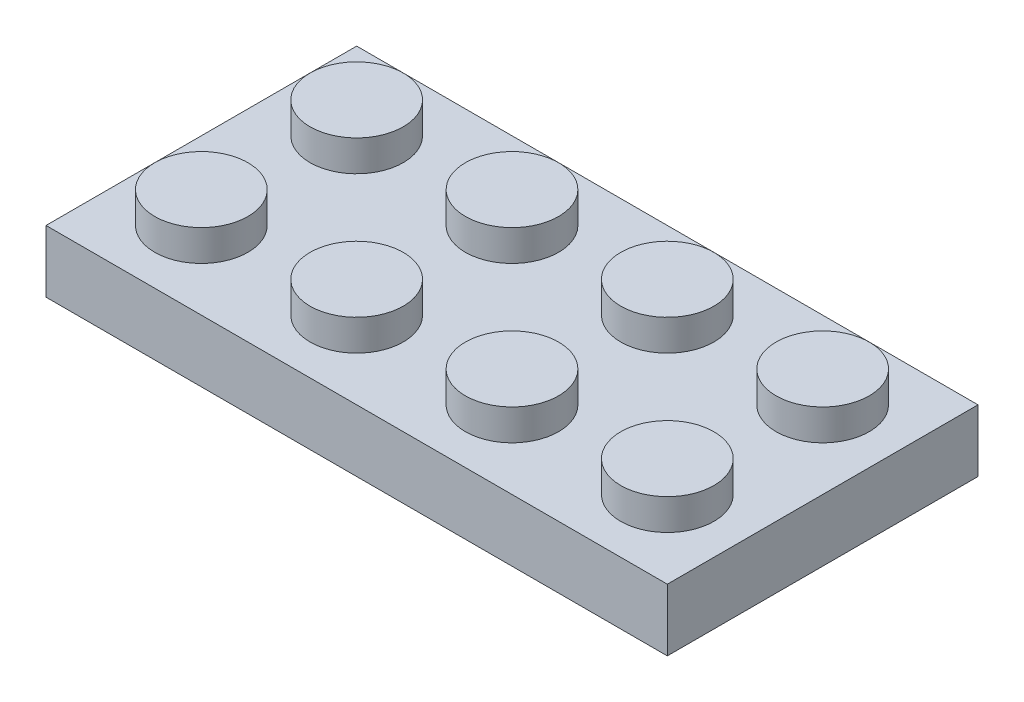
SolidWorks part; units mm, degrees
ref_plane "Front Plane" through (0, 0, 0) normal (0, 0, 1) x (1, 0, 0)
ref_plane "Top Plane" through (0, 0, 0) normal (0, 1, 0) x (1, 0, 0)
ref_plane "Right Plane" through (0, 0, 0) normal (1, 0, 0) x (0, 0, -1)
sketch "Sketch1" plane through (0, 0, 0) normal (0, 1, 0) x (1, 0, 0)
  line L1 (-10, -5) -> (10, -5)
  line L2 (-10, -5) -> (-10, 5)
  line L3 (-10, 5) -> (10, 5)
  line L4 (10, -5) -> (10, 5)
  line L5 (-10, -5) -> (10, 5) construction
  line L6 (-10, 5) -> (10, -5) construction
  line L7 (-9, -4) -> (9, -4)
  line L8 (-9, -4) -> (-9, 4)
  line L9 (-9, 4) -> (9, 4)
  line L10 (9, -4) -> (9, 4)
  line L11 (-9, -4) -> (9, 4) construction
  line L12 (-9, 4) -> (9, -4) construction
  circle A0 centre (-2.5, 2.5) radius 1.5
  circle A1 centre (-7.5, 2.5) radius 1.5
  circle A2 centre (2.5, 2.5) radius 1.5
  circle A3 centre (7.5, 2.5) radius 1.5
  circle A4 centre (-2.5, -2.5) radius 1.5
  circle A5 centre (2.5, -2.5) radius 1.5
  circle A6 centre (7.5, -2.5) radius 1.5
  circle A7 centre (-7.5, -2.5) radius 1.5
  circle A8 centre (-5, 0) radius 2.0355
  circle A9 centre (-5, 0) radius 1.5
  circle A10 centre (0, 0) radius 1.5
  circle A11 centre (0, 0) radius 2.0355
  circle A12 centre (5, 0) radius 1.5
  circle A13 centre (5, 0) radius 2.0355
  circle A14 centre (-7.5, 2.5) radius 0.75
  circle A15 centre (-2.5, 2.5) radius 0.75
  circle A16 centre (2.5, 2.5) radius 0.75
  circle A17 centre (7.5, 2.5) radius 0.75
  circle A18 centre (-2.5, -2.5) radius 0.75
  circle A19 centre (2.5, -2.5) radius 0.75
  circle A20 centre (7.5, -2.5) radius 0.75
  circle A21 centre (-7.5, -2.5) radius 0.75
  point P0 (0, 0)
  point P9 (0, 0)
  dimension "D5" = 1
  dimension "D7" = 4
  dimension "D9" = 3
  dimension "D11" = 1.5
  dimension "D1" = 10
  dimension "D2" = 20
  dimension "D3" = 2.5
  dimension "D4" = 2.5
  dimension "D6" = 1
  dimension "D8" = 2
  dimension "D10" = 3
  dimension "D12" = 4
  dimension "D13" = 2
extrude "Boss-Extrude1" add sketch "Sketch1" along normal blind 2 contours A1 | A0 | A2 | A3 | A6 | A5 | A4 | A7 | A14 | A15 | A16 | A17 | A20 | A19 | A18 | A21 region at (-8.5307, 0, 3.5307) region at (-3.8466, 0, 3.0578) region at (-8.5307, 0, -3.5307) region at (1.1534, 0, 3.0578) region at (6.1534, 0, 3.0578) region at (-1.4693, 0, -3.5307) region at (3.5307, 0, -3.5307) region at (8.0578, 0, -1.1534) region at (-7.5, 0, -2.5) region at (-2.5, 0, -2.5) region at (2.5, 0, -2.5) region at (7.5, 0, -2.5) region at (-2.5, 0, 2.5) region at (2.5, 0, 2.5) region at (7.5, 0, 2.5) region at (-7.5, 0, 2.5)
extrude "Boss-Extrude2" add sketch "Sketch1<3>" along normal blind 1 contours L2 L3 L4 L1
sketch "Sketch1<3>" plane through (0, 0, 0) normal (0, 1, 0) x (1, 0, 0) same geometry as "Sketch1"
extrude "Cut-Extrude1" cut sketch "Sketch1<4>" along normal blind 1 contours A14 | A21 | A18 | A15 | A19 | A16 | A20 | A17 region at (-7.5, 0, -2.5) region at (-2.5, 0, -2.5) region at (2.5, 0, -2.5) region at (7.5, 0, -2.5) region at (-2.5, 0, 2.5) region at (2.5, 0, 2.5) region at (7.5, 0, 2.5) region at (-7.5, 0, 2.5)
sketch "Sketch1<4>" plane through (0, 0, 0) normal (0, 1, 0) x (1, 0, 0) same geometry as "Sketch1"
extrude "Boss-Extrude3" add sketch "Sketch1<5>" against normal blind 1 contours A8 A9 | A11 A10 | A13 A12 | L1 L4 L3 L2 L10 L7 L8 L9 region at (-9.7764, 0, 0) region at (-6.978, 0, 0) region at (0, 0, 1.978) region at (5, 0, 1.978)
sketch "Sketch1<5>" plane through (0, 0, 0) normal (0, 1, 0) x (1, 0, 0) same geometry as "Sketch1"
